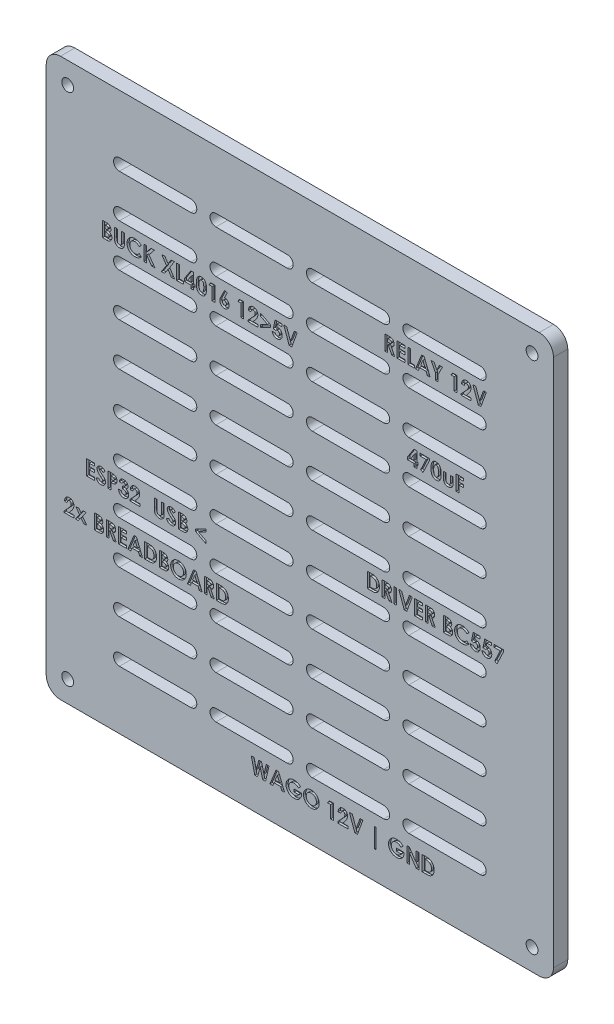
SolidWorks part; units mm, degrees
ref_plane "Front Plane" through (0, 0, 0) normal (0, 0, 1) x (1, 0, 0)
ref_plane "Top Plane" through (0, 0, 0) normal (0, 1, 0) x (1, 0, 0)
ref_plane "Right Plane" through (0, 0, 0) normal (1, 0, 0) x (0, 0, -1)
sketch "Sketch1" plane through (0, 0, 0) normal (0, 0, 1) x (1, 0, 0)
  line L0 (-67, 40) -> (67, 40)
  line L1 (71, 44) -> (71, 192)
  line L2 (67, 196) -> (-67, 196)
  line L3 (-71, 192) -> (-71, 44)
  arc A0 (-71, 44) -> (-67, 40) centre (-67, 44) ccw
  arc A1 (67, 40) -> (71, 44) centre (67, 44) ccw
  arc A2 (71, 192) -> (67, 196) centre (67, 192) ccw
  arc A3 (-67, 196) -> (-71, 192) centre (-67, 192) ccw
extrude "Plate" add sketch "Sketch1" along normal blind 4
sketch "Sketch2" plane through (0, 0, 0) normal (0, 0, 1) x (1, 0, 0)
  line L0 (-50.5, 58) -> (-30.5, 58) construction
  line L1 (-50.5, 59.65) -> (-30.5, 59.65)
  line L2 (-50.5, 56.35) -> (-30.5, 56.35)
  line L3 (-23.5, 58) -> (-3.5, 58) construction
  line L4 (-23.5, 59.65) -> (-3.5, 59.65)
  line L5 (-23.5, 56.35) -> (-3.5, 56.35)
  line L6 (3.5, 58) -> (23.5, 58) construction
  line L7 (3.5, 59.65) -> (23.5, 59.65)
  line L8 (3.5, 56.35) -> (23.5, 56.35)
  line L9 (30.5, 58) -> (50.5, 58) construction
  line L10 (30.5, 59.65) -> (50.5, 59.65)
  line L11 (30.5, 56.35) -> (50.5, 56.35)
  line L12 (-50.5, 70) -> (-30.5, 70) construction
  line L13 (-50.5, 71.65) -> (-30.5, 71.65)
  line L14 (-50.5, 68.35) -> (-30.5, 68.35)
  line L15 (-23.5, 70) -> (-3.5, 70) construction
  line L16 (-23.5, 71.65) -> (-3.5, 71.65)
  line L17 (-23.5, 68.35) -> (-3.5, 68.35)
  line L18 (3.5, 70) -> (23.5, 70) construction
  line L19 (3.5, 71.65) -> (23.5, 71.65)
  line L20 (3.5, 68.35) -> (23.5, 68.35)
  line L21 (30.5, 70) -> (50.5, 70) construction
  line L22 (30.5, 71.65) -> (50.5, 71.65)
  line L23 (30.5, 68.35) -> (50.5, 68.35)
  line L24 (-50.5, 82) -> (-30.5, 82) construction
  line L25 (-50.5, 83.65) -> (-30.5, 83.65)
  line L26 (-50.5, 80.35) -> (-30.5, 80.35)
  line L27 (-23.5, 82) -> (-3.5, 82) construction
  line L28 (-23.5, 83.65) -> (-3.5, 83.65)
  line L29 (-23.5, 80.35) -> (-3.5, 80.35)
  line L30 (3.5, 82) -> (23.5, 82) construction
  line L31 (3.5, 83.65) -> (23.5, 83.65)
  line L32 (3.5, 80.35) -> (23.5, 80.35)
  line L33 (30.5, 82) -> (50.5, 82) construction
  line L34 (30.5, 83.65) -> (50.5, 83.65)
  line L35 (30.5, 80.35) -> (50.5, 80.35)
  line L36 (-50.5, 94) -> (-30.5, 94) construction
  line L37 (-50.5, 95.65) -> (-30.5, 95.65)
  line L38 (-50.5, 92.35) -> (-30.5, 92.35)
  line L39 (-23.5, 94) -> (-3.5, 94) construction
  line L40 (-23.5, 95.65) -> (-3.5, 95.65)
  line L41 (-23.5, 92.35) -> (-3.5, 92.35)
  line L42 (3.5, 94) -> (23.5, 94) construction
  line L43 (3.5, 95.65) -> (23.5, 95.65)
  line L44 (3.5, 92.35) -> (23.5, 92.35)
  line L45 (30.5, 94) -> (50.5, 94) construction
  line L46 (30.5, 95.65) -> (50.5, 95.65)
  line L47 (30.5, 92.35) -> (50.5, 92.35)
  line L48 (-50.5, 106) -> (-30.5, 106) construction
  line L49 (-50.5, 107.65) -> (-30.5, 107.65)
  line L50 (-50.5, 104.35) -> (-30.5, 104.35)
  line L51 (-23.5, 106) -> (-3.5, 106) construction
  line L52 (-23.5, 107.65) -> (-3.5, 107.65)
  line L53 (-23.5, 104.35) -> (-3.5, 104.35)
  line L54 (3.5, 106) -> (23.5, 106) construction
  line L55 (3.5, 107.65) -> (23.5, 107.65)
  line L56 (3.5, 104.35) -> (23.5, 104.35)
  line L57 (30.5, 106) -> (50.5, 106) construction
  line L58 (30.5, 107.65) -> (50.5, 107.65)
  line L59 (30.5, 104.35) -> (50.5, 104.35)
  line L60 (-50.5, 118) -> (-30.5, 118) construction
  line L61 (-50.5, 119.65) -> (-30.5, 119.65)
  line L62 (-50.5, 116.35) -> (-30.5, 116.35)
  line L63 (-23.5, 118) -> (-3.5, 118) construction
  line L64 (-23.5, 119.65) -> (-3.5, 119.65)
  line L65 (-23.5, 116.35) -> (-3.5, 116.35)
  line L66 (3.5, 118) -> (23.5, 118) construction
  line L67 (3.5, 119.65) -> (23.5, 119.65)
  line L68 (3.5, 116.35) -> (23.5, 116.35)
  line L69 (30.5, 118) -> (50.5, 118) construction
  line L70 (30.5, 119.65) -> (50.5, 119.65)
  line L71 (30.5, 116.35) -> (50.5, 116.35)
  line L72 (-50.5, 130) -> (-30.5, 130) construction
  line L73 (-50.5, 131.65) -> (-30.5, 131.65)
  line L74 (-50.5, 128.35) -> (-30.5, 128.35)
  line L75 (-23.5, 130) -> (-3.5, 130) construction
  line L76 (-23.5, 131.65) -> (-3.5, 131.65)
  line L77 (-23.5, 128.35) -> (-3.5, 128.35)
  line L78 (3.5, 130) -> (23.5, 130) construction
  line L79 (3.5, 131.65) -> (23.5, 131.65)
  line L80 (3.5, 128.35) -> (23.5, 128.35)
  line L81 (30.5, 130) -> (50.5, 130) construction
  line L82 (30.5, 131.65) -> (50.5, 131.65)
  line L83 (30.5, 128.35) -> (50.5, 128.35)
  line L84 (-50.5, 142) -> (-30.5, 142) construction
  line L85 (-50.5, 143.65) -> (-30.5, 143.65)
  line L86 (-50.5, 140.35) -> (-30.5, 140.35)
  line L87 (-23.5, 142) -> (-3.5, 142) construction
  line L88 (-23.5, 143.65) -> (-3.5, 143.65)
  line L89 (-23.5, 140.35) -> (-3.5, 140.35)
  line L90 (3.5, 142) -> (23.5, 142) construction
  line L91 (3.5, 143.65) -> (23.5, 143.65)
  line L92 (3.5, 140.35) -> (23.5, 140.35)
  line L93 (30.5, 142) -> (50.5, 142) construction
  line L94 (30.5, 143.65) -> (50.5, 143.65)
  line L95 (30.5, 140.35) -> (50.5, 140.35)
  line L96 (-50.5, 154) -> (-30.5, 154) construction
  line L97 (-50.5, 155.65) -> (-30.5, 155.65)
  line L98 (-50.5, 152.35) -> (-30.5, 152.35)
  line L99 (-23.5, 154) -> (-3.5, 154) construction
  line L100 (-23.5, 155.65) -> (-3.5, 155.65)
  line L101 (-23.5, 152.35) -> (-3.5, 152.35)
  line L102 (3.5, 154) -> (23.5, 154) construction
  line L103 (3.5, 155.65) -> (23.5, 155.65)
  line L104 (3.5, 152.35) -> (23.5, 152.35)
  line L105 (30.5, 154) -> (50.5, 154) construction
  line L106 (30.5, 155.65) -> (50.5, 155.65)
  line L107 (30.5, 152.35) -> (50.5, 152.35)
  line L108 (-50.5, 166) -> (-30.5, 166) construction
  line L109 (-50.5, 167.65) -> (-30.5, 167.65)
  line L110 (-50.5, 164.35) -> (-30.5, 164.35)
  line L111 (-23.5, 166) -> (-3.5, 166) construction
  line L112 (-23.5, 167.65) -> (-3.5, 167.65)
  line L113 (-23.5, 164.35) -> (-3.5, 164.35)
  line L114 (3.5, 166) -> (23.5, 166) construction
  line L115 (3.5, 167.65) -> (23.5, 167.65)
  line L116 (3.5, 164.35) -> (23.5, 164.35)
  line L117 (30.5, 166) -> (50.5, 166) construction
  line L118 (30.5, 167.65) -> (50.5, 167.65)
  line L119 (30.5, 164.35) -> (50.5, 164.35)
  line L120 (-50.5, 178) -> (-30.5, 178) construction
  line L121 (-50.5, 179.65) -> (-30.5, 179.65)
  line L122 (-50.5, 176.35) -> (-30.5, 176.35)
  line L123 (-23.5, 178) -> (-3.5, 178) construction
  line L124 (-23.5, 179.65) -> (-3.5, 179.65)
  line L125 (-23.5, 176.35) -> (-3.5, 176.35)
  line L126 (3.5, 178) -> (23.5, 178) construction
  line L127 (3.5, 179.65) -> (23.5, 179.65)
  line L128 (3.5, 176.35) -> (23.5, 176.35)
  line L129 (30.5, 178) -> (50.5, 178) construction
  line L130 (30.5, 179.65) -> (50.5, 179.65)
  line L131 (30.5, 176.35) -> (50.5, 176.35)
  circle A0 centre (-65, 46) radius 1.65
  circle A1 centre (65, 46) radius 1.65
  circle A2 centre (-65, 190) radius 1.65
  circle A3 centre (65, 190) radius 1.65
  arc A4 (-50.5, 59.65) -> (-50.5, 56.35) centre (-50.5, 58) ccw
  arc A5 (-30.5, 56.35) -> (-30.5, 59.65) centre (-30.5, 58) ccw
  arc A6 (-23.5, 59.65) -> (-23.5, 56.35) centre (-23.5, 58) ccw
  arc A7 (-3.5, 56.35) -> (-3.5, 59.65) centre (-3.5, 58) ccw
  arc A8 (3.5, 59.65) -> (3.5, 56.35) centre (3.5, 58) ccw
  arc A9 (23.5, 56.35) -> (23.5, 59.65) centre (23.5, 58) ccw
  arc A10 (30.5, 59.65) -> (30.5, 56.35) centre (30.5, 58) ccw
  arc A11 (50.5, 56.35) -> (50.5, 59.65) centre (50.5, 58) ccw
  arc A12 (-50.5, 71.65) -> (-50.5, 68.35) centre (-50.5, 70) ccw
  arc A13 (-30.5, 68.35) -> (-30.5, 71.65) centre (-30.5, 70) ccw
  arc A14 (-23.5, 71.65) -> (-23.5, 68.35) centre (-23.5, 70) ccw
  arc A15 (-3.5, 68.35) -> (-3.5, 71.65) centre (-3.5, 70) ccw
  arc A16 (3.5, 71.65) -> (3.5, 68.35) centre (3.5, 70) ccw
  arc A17 (23.5, 68.35) -> (23.5, 71.65) centre (23.5, 70) ccw
  arc A18 (30.5, 71.65) -> (30.5, 68.35) centre (30.5, 70) ccw
  arc A19 (50.5, 68.35) -> (50.5, 71.65) centre (50.5, 70) ccw
  arc A20 (-50.5, 83.65) -> (-50.5, 80.35) centre (-50.5, 82) ccw
  arc A21 (-30.5, 80.35) -> (-30.5, 83.65) centre (-30.5, 82) ccw
  arc A22 (-23.5, 83.65) -> (-23.5, 80.35) centre (-23.5, 82) ccw
  arc A23 (-3.5, 80.35) -> (-3.5, 83.65) centre (-3.5, 82) ccw
  arc A24 (3.5, 83.65) -> (3.5, 80.35) centre (3.5, 82) ccw
  arc A25 (23.5, 80.35) -> (23.5, 83.65) centre (23.5, 82) ccw
  arc A26 (30.5, 83.65) -> (30.5, 80.35) centre (30.5, 82) ccw
  arc A27 (50.5, 80.35) -> (50.5, 83.65) centre (50.5, 82) ccw
  arc A28 (-50.5, 95.65) -> (-50.5, 92.35) centre (-50.5, 94) ccw
  arc A29 (-30.5, 92.35) -> (-30.5, 95.65) centre (-30.5, 94) ccw
  arc A30 (-23.5, 95.65) -> (-23.5, 92.35) centre (-23.5, 94) ccw
  arc A31 (-3.5, 92.35) -> (-3.5, 95.65) centre (-3.5, 94) ccw
  arc A32 (3.5, 95.65) -> (3.5, 92.35) centre (3.5, 94) ccw
  arc A33 (23.5, 92.35) -> (23.5, 95.65) centre (23.5, 94) ccw
  arc A34 (30.5, 95.65) -> (30.5, 92.35) centre (30.5, 94) ccw
  arc A35 (50.5, 92.35) -> (50.5, 95.65) centre (50.5, 94) ccw
  arc A36 (-50.5, 107.65) -> (-50.5, 104.35) centre (-50.5, 106) ccw
  arc A37 (-30.5, 104.35) -> (-30.5, 107.65) centre (-30.5, 106) ccw
  arc A38 (-23.5, 107.65) -> (-23.5, 104.35) centre (-23.5, 106) ccw
  arc A39 (-3.5, 104.35) -> (-3.5, 107.65) centre (-3.5, 106) ccw
  arc A40 (3.5, 107.65) -> (3.5, 104.35) centre (3.5, 106) ccw
  arc A41 (23.5, 104.35) -> (23.5, 107.65) centre (23.5, 106) ccw
  arc A42 (30.5, 107.65) -> (30.5, 104.35) centre (30.5, 106) ccw
  arc A43 (50.5, 104.35) -> (50.5, 107.65) centre (50.5, 106) ccw
  arc A44 (-50.5, 119.65) -> (-50.5, 116.35) centre (-50.5, 118) ccw
  arc A45 (-30.5, 116.35) -> (-30.5, 119.65) centre (-30.5, 118) ccw
  arc A46 (-23.5, 119.65) -> (-23.5, 116.35) centre (-23.5, 118) ccw
  arc A47 (-3.5, 116.35) -> (-3.5, 119.65) centre (-3.5, 118) ccw
  arc A48 (3.5, 119.65) -> (3.5, 116.35) centre (3.5, 118) ccw
  arc A49 (23.5, 116.35) -> (23.5, 119.65) centre (23.5, 118) ccw
  arc A50 (30.5, 119.65) -> (30.5, 116.35) centre (30.5, 118) ccw
  arc A51 (50.5, 116.35) -> (50.5, 119.65) centre (50.5, 118) ccw
  arc A52 (-50.5, 131.65) -> (-50.5, 128.35) centre (-50.5, 130) ccw
  arc A53 (-30.5, 128.35) -> (-30.5, 131.65) centre (-30.5, 130) ccw
  arc A54 (-23.5, 131.65) -> (-23.5, 128.35) centre (-23.5, 130) ccw
  arc A55 (-3.5, 128.35) -> (-3.5, 131.65) centre (-3.5, 130) ccw
  arc A56 (3.5, 131.65) -> (3.5, 128.35) centre (3.5, 130) ccw
  arc A57 (23.5, 128.35) -> (23.5, 131.65) centre (23.5, 130) ccw
  arc A58 (30.5, 131.65) -> (30.5, 128.35) centre (30.5, 130) ccw
  arc A59 (50.5, 128.35) -> (50.5, 131.65) centre (50.5, 130) ccw
  arc A60 (-50.5, 143.65) -> (-50.5, 140.35) centre (-50.5, 142) ccw
  arc A61 (-30.5, 140.35) -> (-30.5, 143.65) centre (-30.5, 142) ccw
  arc A62 (-23.5, 143.65) -> (-23.5, 140.35) centre (-23.5, 142) ccw
  arc A63 (-3.5, 140.35) -> (-3.5, 143.65) centre (-3.5, 142) ccw
  arc A64 (3.5, 143.65) -> (3.5, 140.35) centre (3.5, 142) ccw
  arc A65 (23.5, 140.35) -> (23.5, 143.65) centre (23.5, 142) ccw
  arc A66 (30.5, 143.65) -> (30.5, 140.35) centre (30.5, 142) ccw
  arc A67 (50.5, 140.35) -> (50.5, 143.65) centre (50.5, 142) ccw
  arc A68 (-50.5, 155.65) -> (-50.5, 152.35) centre (-50.5, 154) ccw
  arc A69 (-30.5, 152.35) -> (-30.5, 155.65) centre (-30.5, 154) ccw
  arc A70 (-23.5, 155.65) -> (-23.5, 152.35) centre (-23.5, 154) ccw
  arc A71 (-3.5, 152.35) -> (-3.5, 155.65) centre (-3.5, 154) ccw
  arc A72 (3.5, 155.65) -> (3.5, 152.35) centre (3.5, 154) ccw
  arc A73 (23.5, 152.35) -> (23.5, 155.65) centre (23.5, 154) ccw
  arc A74 (30.5, 155.65) -> (30.5, 152.35) centre (30.5, 154) ccw
  arc A75 (50.5, 152.35) -> (50.5, 155.65) centre (50.5, 154) ccw
  arc A76 (-50.5, 167.65) -> (-50.5, 164.35) centre (-50.5, 166) ccw
  arc A77 (-30.5, 164.35) -> (-30.5, 167.65) centre (-30.5, 166) ccw
  arc A78 (-23.5, 167.65) -> (-23.5, 164.35) centre (-23.5, 166) ccw
  arc A79 (-3.5, 164.35) -> (-3.5, 167.65) centre (-3.5, 166) ccw
  arc A80 (3.5, 167.65) -> (3.5, 164.35) centre (3.5, 166) ccw
  arc A81 (23.5, 164.35) -> (23.5, 167.65) centre (23.5, 166) ccw
  arc A82 (30.5, 167.65) -> (30.5, 164.35) centre (30.5, 166) ccw
  arc A83 (50.5, 164.35) -> (50.5, 167.65) centre (50.5, 166) ccw
  arc A84 (-50.5, 179.65) -> (-50.5, 176.35) centre (-50.5, 178) ccw
  arc A85 (-30.5, 176.35) -> (-30.5, 179.65) centre (-30.5, 178) ccw
  arc A86 (-23.5, 179.65) -> (-23.5, 176.35) centre (-23.5, 178) ccw
  arc A87 (-3.5, 176.35) -> (-3.5, 179.65) centre (-3.5, 178) ccw
  arc A88 (3.5, 179.65) -> (3.5, 176.35) centre (3.5, 178) ccw
  arc A89 (23.5, 176.35) -> (23.5, 179.65) centre (23.5, 178) ccw
  arc A90 (30.5, 179.65) -> (30.5, 176.35) centre (30.5, 178) ccw
  arc A91 (50.5, 176.35) -> (50.5, 179.65) centre (50.5, 178) ccw
  point P10 (-40.5, 58)
  point P15 (-13.5, 58)
  point P22 (13.5, 58)
  point P29 (40.5, 58)
  point P36 (-40.5, 70)
  point P43 (-13.5, 70)
  point P50 (13.5, 70)
  point P57 (40.5, 70)
  point P64 (-40.5, 82)
  point P71 (-13.5, 82)
  point P78 (13.5, 82)
  point P85 (40.5, 82)
  point P92 (-40.5, 94)
  point P99 (-13.5, 94)
  point P106 (13.5, 94)
  point P113 (40.5, 94)
  point P120 (-40.5, 106)
  point P127 (-13.5, 106)
  point P134 (13.5, 106)
  point P141 (40.5, 106)
  point P148 (-40.5, 118)
  point P155 (-13.5, 118)
  point P162 (13.5, 118)
  point P169 (40.5, 118)
  point P176 (-40.5, 130)
  point P183 (-13.5, 130)
  point P190 (13.5, 130)
  point P197 (40.5, 130)
  point P204 (-40.5, 142)
  point P211 (-13.5, 142)
  point P218 (13.5, 142)
  point P225 (40.5, 142)
  point P232 (-40.5, 154)
  point P239 (-13.5, 154)
  point P246 (13.5, 154)
  point P253 (40.5, 154)
  point P260 (-40.5, 166)
  point P267 (-13.5, 166)
  point P274 (13.5, 166)
  point P281 (40.5, 166)
  point P288 (-40.5, 178)
  point P295 (-13.5, 178)
  point P302 (13.5, 178)
  point P309 (40.5, 178)
  point P316 (0, 0)
extrude "Mounting slots" cut sketch "Sketch2" along normal through all
ref_plane "P1_Front_4" through (0, 0, 4) normal (0, 0, 1) x (1, 0, 0)
sketch "Sketch3" plane through (0, 0, 4) normal (0, 0, 1) x (1, 0, 0)
  text T0 "BUCK XL4016 12>5V" font "Century Gothic" height 4.2
  text T1 "RELAY 12V" font "Century Gothic" height 4.2
  text T2 "470uF" font "Century Gothic" height 4.2
  text T3 "ESP32  USB <" font "Century Gothic" height 4.2
  text T4 "2x BREADBOARD" font "Century Gothic" height 4.2
  text T5 "DRIVER BC557" font "Century Gothic" height 4.2
  text T6 "WAGO 12V | GND" font "Century Gothic" height 4.2
extrude "Zone labels" cut sketch "Sketch3" against normal blind 0.6
